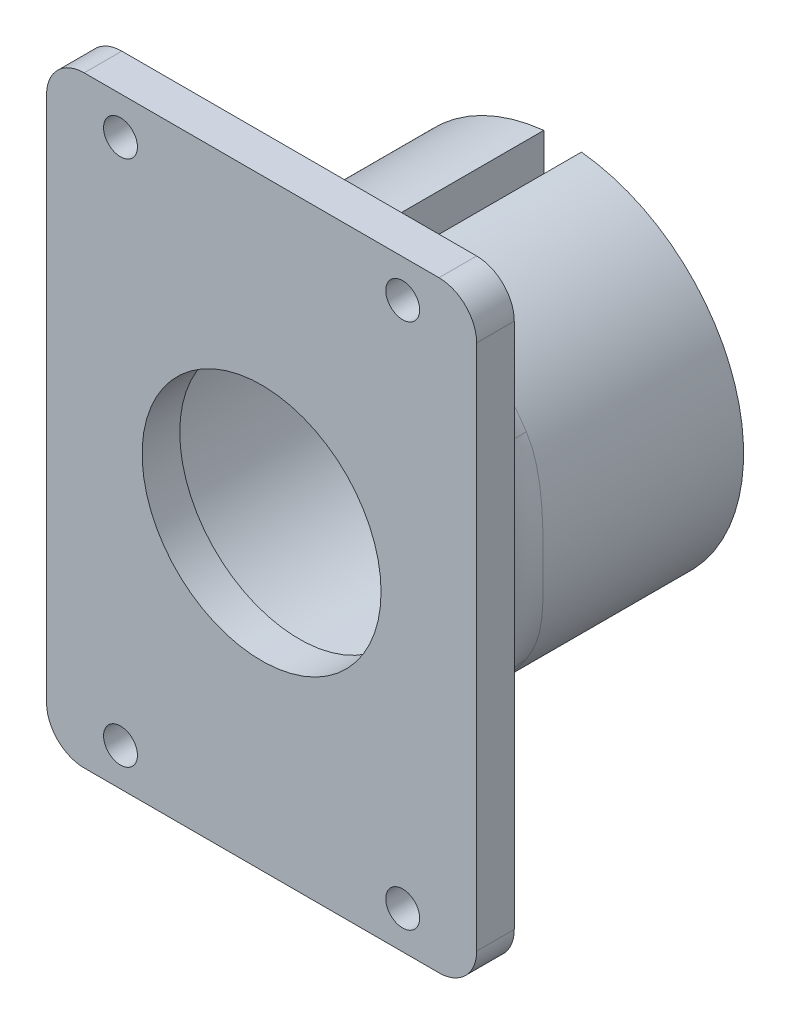
SolidWorks part; units mm, degrees
ref_plane "Front" through (0, 0, 0) normal (0, 0, 1) x (1, 0, 0)
ref_plane "Top" through (0, 0, 0) normal (0, 1, 0) x (1, 0, 0)
ref_plane "Right" through (0, 0, 0) normal (1, 0, 0) x (0, 0, -1)
sketch "Sketch1" plane through (0, 0, 0) normal (0, 0, 1) x (1, 0, 0)
  line L1 (-28.575, -40) -> (28.575, -40)
  line L2 (-28.575, -40) -> (-28.575, 40)
  line L3 (-28.575, 40) -> (28.575, 40)
  line L4 (28.575, -40) -> (28.575, 40)
  line L5 (-28.575, -40) -> (28.575, 40) construction
  line L6 (-28.575, 40) -> (28.575, -40) construction
  point P0 (0, 0)
  dimension "D1" = 80
  dimension "D2" = 57.15
extrude "Boss-Extrude1" add sketch "Sketch1" along normal blind 5
sketch "Sketch2" plane through (0, 0, 5) normal (0, 0, 1) x (1, 0, 0)
  line L0 (0, 40) -> (0, -40) construction
  line L1 (28.575, 40) -> (-28.575, 40) construction
  line L2 (-28.575, -40) -> (28.575, -40) construction
  line L3 (-28.575, 40) -> (-28.575, -40) construction
  line L4 (-28.575, 0) -> (28.575, 0) construction
  line L5 (28.575, -40) -> (28.575, 40) construction
  circle A0 centre (-18.75, 35) radius 2.25
  circle A1 centre (18.75, 35) radius 2.25
  circle A2 centre (-18.75, -35) radius 2.25
  circle A3 centre (18.75, -35) radius 2.25
  dimension "D1" = 5
  dimension "D2" = 4.5
  dimension "D3" = 9.825
extrude "Cut-Extrude1" cut sketch "Sketch2" against normal up to next
fillet "Fillet1" radius 5 4 edges at (-28.575, -40, 2.5) (28.575, -40, 2.5) (28.575, 40, 2.5) (-28.575, 40, 2.5)
sketch "Sketch3" plane through (0, 0, 5) normal (0, 0, 1) x (1, 0, 0)
  line L0 (28.575, 0) -> (-28.575, 0) construction
  line L1 (28.575, -35) -> (28.575, 35) construction
  line L2 (-28.575, 35) -> (-28.575, -35) construction
  circle A0 centre (0, 0) radius 15.875
  dimension "D1" = 31.75
extrude "Cut-Extrude2" cut sketch "Sketch3" against normal up to next
sketch "Sketch4" plane through (0, 0, 0) normal (0, 0, -1) x (-1, 0, 0)
  circle A0 centre (0, 0) radius 19.05
  circle A1 centre (0, 0) radius 24.05
  dimension "D1" = 38.1
  dimension "D2" = 5
extrude "Boss-Extrude2" add sketch "Sketch4" along normal blind 35
sketch "Sketch5" plane through (0, 0, -35) normal (0, 0, -1) x (-1, 0, 0)
  line L0 (0, 24.05) -> (0, -24.05) construction
  line L1 (-2.5, 24.05) -> (-2.5, -24.05)
  line L2 (2.5, 24.05) -> (2.5, -24.05)
  line L3 (-2.5, 24.05) -> (2.5, 24.05)
  line L4 (-2.5, -24.05) -> (2.5, -24.05)
  circle A0 centre (0, 0) radius 24.05 construction
  dimension "D1" = 2.5
  dimension "D2" = 2.5
extrude "Cut-Extrude3" cut sketch "Sketch5" against normal blind 20
fillet "Fillet2" radius 10 1 edges at (-24.05, 0, 0)
